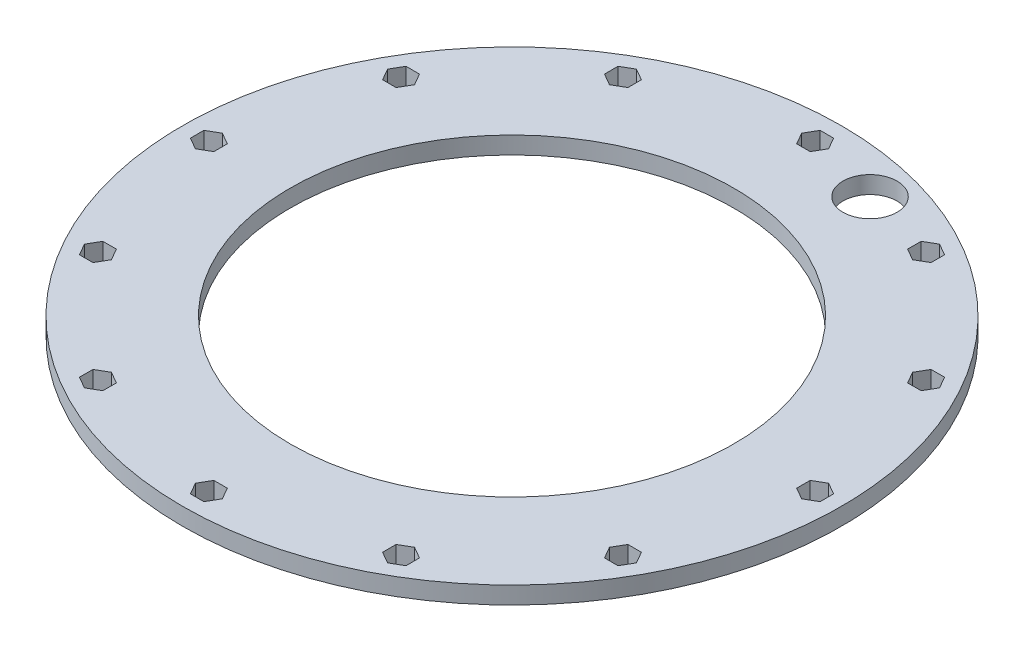
SolidWorks part; units mm, degrees
material "Balsa"
ref_plane "Ebene vorne" through (0, 0, 0) normal (0, 0, 1) x (1, 0, 0)
ref_plane "Ebene oben" through (0, 0, 0) normal (0, 1, 0) x (1, 0, 0)
ref_plane "Ebene rechts" through (0, 0, 0) normal (1, 0, 0) x (0, 0, -1)
sketch "Sketch1" plane through (0, 0, 0) normal (0, 1, 0) x (1, 0, 0)
  circle A0 centre (0, 0) radius 51.2
  circle A1 centre (0, 0) radius 76.1
  dimension "D1" = 152.2
  dimension "D2" = 102.4
extrude "Boss-Extrude1" add sketch "Sketch1" along normal blind 4
sketch "Sketch2" plane through (0, 4, 0) normal (0, 1, 0) x (1, 0, 0)
  line L0 (37.7, 59.0629) -> (37.7, 62.1806)
  line L1 (3.1177, 70) -> (1.5588, 72.7)
  line L2 (1.5588, 72.7) -> (-1.5588, 72.7)
  line L3 (-1.5588, 72.7) -> (-3.1177, 70)
  line L4 (-3.1177, 70) -> (-1.5588, 67.3)
  line L5 (-1.5588, 67.3) -> (1.5588, 67.3)
  line L6 (1.5588, 67.3) -> (3.1177, 70)
  line L7 (37.7, 62.1806) -> (35, 63.7395)
  line L8 (35, 63.7395) -> (32.3, 62.1806)
  line L9 (32.3, 62.1806) -> (32.3, 59.0629)
  line L10 (32.3, 59.0629) -> (35, 57.5041)
  line L11 (35, 57.5041) -> (37.7, 59.0629)
  line L12 (62.1806, 32.3) -> (63.7395, 35)
  line L13 (63.7395, 35) -> (62.1806, 37.7)
  line L14 (62.1806, 37.7) -> (59.0629, 37.7)
  line L15 (59.0629, 37.7) -> (57.5041, 35)
  line L16 (57.5041, 35) -> (59.0629, 32.3)
  line L17 (59.0629, 32.3) -> (62.1806, 32.3)
  line L18 (70, -3.1177) -> (72.7, -1.5588)
  line L19 (72.7, -1.5588) -> (72.7, 1.5588)
  line L20 (72.7, 1.5588) -> (70, 3.1177)
  line L21 (70, 3.1177) -> (67.3, 1.5588)
  line L22 (67.3, 1.5588) -> (67.3, -1.5588)
  line L23 (67.3, -1.5588) -> (70, -3.1177)
  line L24 (59.0629, -37.7) -> (62.1806, -37.7)
  line L25 (62.1806, -37.7) -> (63.7395, -35)
  line L26 (63.7395, -35) -> (62.1806, -32.3)
  line L27 (62.1806, -32.3) -> (59.0629, -32.3)
  line L28 (59.0629, -32.3) -> (57.5041, -35)
  line L29 (57.5041, -35) -> (59.0629, -37.7)
  line L30 (32.3, -62.1806) -> (35, -63.7395)
  line L31 (35, -63.7395) -> (37.7, -62.1806)
  line L32 (37.7, -62.1806) -> (37.7, -59.0629)
  line L33 (37.7, -59.0629) -> (35, -57.5041)
  line L34 (35, -57.5041) -> (32.3, -59.0629)
  line L35 (32.3, -59.0629) -> (32.3, -62.1806)
  line L36 (-3.1177, -70) -> (-1.5588, -72.7)
  line L37 (-1.5588, -72.7) -> (1.5588, -72.7)
  line L38 (1.5588, -72.7) -> (3.1177, -70)
  line L39 (3.1177, -70) -> (1.5588, -67.3)
  line L40 (1.5588, -67.3) -> (-1.5588, -67.3)
  line L41 (-1.5588, -67.3) -> (-3.1177, -70)
  line L42 (-37.7, -59.0629) -> (-37.7, -62.1806)
  line L43 (-37.7, -62.1806) -> (-35, -63.7395)
  line L44 (-35, -63.7395) -> (-32.3, -62.1806)
  line L45 (-32.3, -62.1806) -> (-32.3, -59.0629)
  line L46 (-32.3, -59.0629) -> (-35, -57.5041)
  line L47 (-35, -57.5041) -> (-37.7, -59.0629)
  line L48 (-62.1806, -32.3) -> (-63.7395, -35)
  line L49 (-63.7395, -35) -> (-62.1806, -37.7)
  line L50 (-62.1806, -37.7) -> (-59.0629, -37.7)
  line L51 (-59.0629, -37.7) -> (-57.5041, -35)
  line L52 (-57.5041, -35) -> (-59.0629, -32.3)
  line L53 (-59.0629, -32.3) -> (-62.1806, -32.3)
  line L54 (-70, 3.1177) -> (-72.7, 1.5588)
  line L55 (-72.7, 1.5588) -> (-72.7, -1.5588)
  line L56 (-72.7, -1.5588) -> (-70, -3.1177)
  line L57 (-70, -3.1177) -> (-67.3, -1.5588)
  line L58 (-67.3, -1.5588) -> (-67.3, 1.5588)
  line L59 (-67.3, 1.5588) -> (-70, 3.1177)
  line L60 (-59.0629, 37.7) -> (-62.1806, 37.7)
  line L61 (-62.1806, 37.7) -> (-63.7395, 35)
  line L62 (-63.7395, 35) -> (-62.1806, 32.3)
  line L63 (-62.1806, 32.3) -> (-59.0629, 32.3)
  line L64 (-59.0629, 32.3) -> (-57.5041, 35)
  line L65 (-57.5041, 35) -> (-59.0629, 37.7)
  line L66 (-32.3, 62.1806) -> (-35, 63.7395)
  line L67 (-35, 63.7395) -> (-37.7, 62.1806)
  line L68 (-37.7, 62.1806) -> (-37.7, 59.0629)
  line L69 (-37.7, 59.0629) -> (-35, 57.5041)
  line L70 (-35, 57.5041) -> (-32.3, 59.0629)
  line L71 (-32.3, 59.0629) -> (-32.3, 62.1806)
  circle A0 centre (35, 60.6218) radius 2.7 construction
  circle A1 centre (60.6218, 35) radius 2.7 construction
  circle A2 centre (70, 0) radius 2.7 construction
  circle A3 centre (60.6218, -35) radius 2.7 construction
  circle A4 centre (35, -60.6218) radius 2.7 construction
  circle A5 centre (0, -70) radius 2.7 construction
  circle A7 centre (-35, -60.6218) radius 2.7 construction
  circle A8 centre (-60.6218, -35) radius 2.7 construction
  circle A9 centre (-70, 0) radius 2.7 construction
  circle A10 centre (-60.6218, 35) radius 2.7 construction
  circle A11 centre (-35, 60.6218) radius 2.7 construction
  circle A12 centre (0, 70) radius 2.7 construction
  point P28 (0, 0)
  point P103 (0, 0)
  dimension "D1" = 5.4
  dimension "D2" = 70
  dimension "D3" = 12
extrude "Cut-Extrude1" cut sketch "Sketch2" against normal through all
sketch "Sketch3" plane through (0, 4, 0) normal (0, 1, 0) x (1, 0, 0)
  line L0 (17.4703, 65.2) -> (0, 0) construction
  line L1 (0, 0) -> (0, 80.521) construction
  circle A0 centre (17.4703, 65.2) radius 6.25
  dimension "D1" = 12.5
  dimension "D3" = 15
  dimension "D2" = 67.5
extrude "Cut-Extrude2" cut sketch "Sketch3" against normal blind 10
